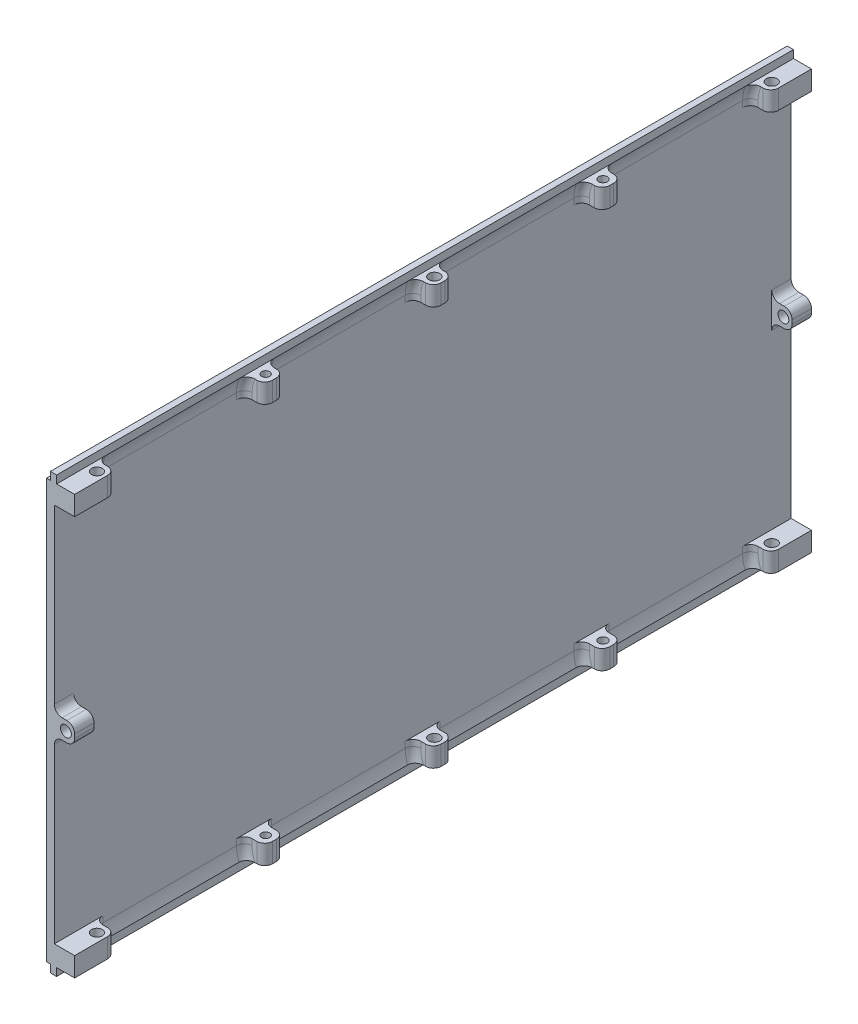
SolidWorks part; units mm, degrees
note: The reader was unsure of these and kept them because the rebuilt part matched: shared geometry of "Sketch4<2>".
ref_plane "Front Plane" through (0, 0, 0) normal (0, 0, 1) x (1, 0, 0)
ref_plane "Top Plane" through (0, 0, 0) normal (0, 1, 0) x (1, 0, 0)
ref_plane "Right Plane" through (0, 0, 0) normal (1, 0, 0) x (0, 0, -1)
sketch "Sketch1" plane through (0, 0, 0) normal (1, 0, 0) x (0, 0, -1)
  line L0 (-95.2867, 0.9102) -> (94.7133, 0.9102) construction
  line L1 (-95.2867, 54.9102) -> (94.7133, 54.9102)
  line L2 (-95.2867, 54.9102) -> (-95.2867, -53.0898)
  line L3 (-95.2867, -53.0898) -> (94.7133, -53.0898)
  line L4 (94.7133, 54.9102) -> (94.7133, -53.0898)
  line L5 (-82.7867, 54.9102) -> (-82.7867, -53.0898) construction
  line L6 (-2.7867, 54.9102) -> (-2.7867, -53.0898) construction
  line L7 (89.2133, 54.9102) -> (89.2133, -53.0898) construction
  dimension "D1" = 190
  dimension "D2" = 108
  dimension "D3" = 12.5
  dimension "D4" = 92.5
  dimension "D5" = 92
extrude "Boss-Extrude1" add sketch "Sketch1" along normal blind 2
sketch "Sketch2" plane through (2, 0, 0) normal (1, 0, 0) x (0, 0, -1)
  line L0 (-0.2867, 54.9102) -> (-0.2867, -53.0898) construction
  line L1 (94.7133, 54.9102) -> (-95.2867, 54.9102) construction
  line L2 (-95.2867, -53.0898) -> (94.7133, -53.0898) construction
  line L3 (-87.2867, 54.9102) -> (-87.2867, -53.0898) construction
  line L4 (86.7133, 54.9102) -> (86.7133, -53.0898) construction
  line L5 (-43.7867, 54.9102) -> (-43.7867, 49.9102) construction
  line L6 (-95.2867, 0.9102) -> (94.7133, 0.9102) construction
  line L7 (-95.2867, 54.9102) -> (-95.2867, -53.0898) construction
  line L8 (94.7133, -53.0898) -> (94.7133, 54.9102) construction
  line L9 (-0.2867, 54.9102) -> (-0.2867, 49.9102) construction
  line L10 (-2.7867, 54.9102) -> (2.2133, 54.9102)
  line L11 (-2.7867, 54.9102) -> (-2.7867, 49.9102)
  line L12 (-2.7867, 49.9102) -> (2.2133, 49.9102)
  line L13 (2.2133, 54.9102) -> (2.2133, 49.9102)
  line L14 (84.2133, 54.9102) -> (89.2133, 54.9102)
  line L15 (84.2133, 54.9102) -> (84.2133, 49.9102)
  line L16 (84.2133, 49.9102) -> (89.2133, 49.9102)
  line L17 (89.2133, 54.9102) -> (89.2133, 49.9102)
  line L18 (-89.7867, 54.9102) -> (-84.7867, 54.9102)
  line L19 (-89.7867, 54.9102) -> (-89.7867, 49.9102)
  line L20 (-89.7867, 49.9102) -> (-84.7867, 49.9102)
  line L21 (-84.7867, 54.9102) -> (-84.7867, 49.9102)
  line L22 (-95.2867, 3.4102) -> (-90.2867, 3.4102)
  line L23 (-95.2867, 3.4102) -> (-95.2867, -1.5898)
  line L24 (-95.2867, -1.5898) -> (-90.2867, -1.5898)
  line L25 (-90.2867, 3.4102) -> (-90.2867, -1.5898)
  line L26 (89.7133, 3.4102) -> (94.7133, 3.4102)
  line L27 (89.7133, 3.4102) -> (89.7133, -1.5898)
  line L28 (89.7133, -1.5898) -> (94.7133, -1.5898)
  line L29 (94.7133, 3.4102) -> (94.7133, -1.5898)
  line L30 (-87.2867, 54.9102) -> (-87.2867, 49.9102) construction
  line L31 (86.7133, 54.9102) -> (86.7133, 49.9102) construction
  line L32 (-95.2867, 0.9102) -> (-90.2867, 0.9102) construction
  line L33 (89.7133, 0.9102) -> (94.7133, 0.9102) construction
  line L34 (86.7133, -53.0898) -> (86.7133, -48.0898) construction
  line L35 (-87.2867, -53.0898) -> (-87.2867, -48.0898) construction
  line L36 (-0.2867, -53.0898) -> (-0.2867, -48.0898) construction
  line L37 (-84.7867, -53.0898) -> (-84.7867, -48.0898)
  line L38 (-89.7867, -48.0898) -> (-84.7867, -48.0898)
  line L39 (-89.7867, -53.0898) -> (-89.7867, -48.0898)
  line L40 (-89.7867, -53.0898) -> (-84.7867, -53.0898)
  line L41 (89.2133, -53.0898) -> (89.2133, -48.0898)
  line L42 (84.2133, -48.0898) -> (89.2133, -48.0898)
  line L43 (84.2133, -53.0898) -> (84.2133, -48.0898)
  line L44 (84.2133, -53.0898) -> (89.2133, -53.0898)
  line L45 (2.2133, -53.0898) -> (2.2133, -48.0898)
  line L46 (-2.7867, -48.0898) -> (2.2133, -48.0898)
  line L47 (-2.7867, -53.0898) -> (-2.7867, -48.0898)
  line L48 (-2.7867, -53.0898) -> (2.2133, -53.0898)
  line L49 (-46.2867, 54.9102) -> (-41.2867, 54.9102)
  line L50 (-89.7867, 54.9102) -> (-95.2867, 54.9102)
  line L51 (-89.7867, 54.9102) -> (-89.7867, 49.9102)
  line L52 (-89.7867, 49.9102) -> (-95.2867, 49.9102)
  line L53 (-95.2867, 54.9102) -> (-95.2867, 49.9102)
  line L54 (-89.7867, -48.0898) -> (-95.2867, -48.0898)
  line L55 (-89.7867, -48.0898) -> (-89.7867, -53.0898)
  line L56 (-89.7867, -53.0898) -> (-95.2867, -53.0898)
  line L57 (-95.2867, -48.0898) -> (-95.2867, -53.0898)
  line L58 (89.2133, 54.9102) -> (94.7133, 54.9102)
  line L59 (89.2133, 54.9102) -> (89.2133, 49.9102)
  line L60 (89.2133, 49.9102) -> (94.7133, 49.9102)
  line L61 (94.7133, 54.9102) -> (94.7133, 49.9102)
  line L62 (89.2133, -48.0898) -> (94.7133, -48.0898)
  line L63 (89.2133, -48.0898) -> (89.2133, -53.0898)
  line L64 (89.2133, -53.0898) -> (94.7133, -53.0898)
  line L65 (94.7133, -48.0898) -> (94.7133, -53.0898)
  line L66 (-46.2867, 54.9102) -> (-46.2867, 49.9102)
  line L67 (-46.2867, 49.9102) -> (-41.2867, 49.9102)
  line L68 (-41.2867, 54.9102) -> (-41.2867, 49.9102)
  line L69 (43.2133, 54.9102) -> (43.2133, 49.9102) construction
  line L70 (40.7133, 54.9102) -> (40.7133, 49.9102)
  line L71 (45.7133, 49.9102) -> (40.7133, 49.9102)
  line L72 (45.7133, 54.9102) -> (45.7133, 49.9102)
  line L73 (45.7133, 54.9102) -> (40.7133, 54.9102)
  line L74 (45.7133, -48.0898) -> (40.7133, -48.0898)
  line L75 (43.2133, -53.0898) -> (43.2133, -48.0898) construction
  line L76 (45.7133, -53.0898) -> (45.7133, -48.0898)
  line L77 (45.7133, -53.0898) -> (40.7133, -53.0898)
  line L78 (40.7133, -53.0898) -> (40.7133, -48.0898)
  line L79 (-43.7867, -53.0898) -> (-43.7867, -48.0898) construction
  line L80 (-41.2867, -53.0898) -> (-41.2867, -48.0898)
  line L81 (-46.2867, -48.0898) -> (-41.2867, -48.0898)
  line L82 (-46.2867, -53.0898) -> (-46.2867, -48.0898)
  line L83 (-46.2867, -53.0898) -> (-41.2867, -53.0898)
  line M26 (-95.2867, 54.9102) -> (-95.2867, -53.0898)
  line M27 (-95.2867, -53.0898) -> (94.7133, -53.0898)
  line M28 (94.7133, -53.0898) -> (94.7133, 54.9102)
  line M29 (94.7133, 54.9102) -> (-95.2867, 54.9102)
  dimension "D1" = 87
  dimension "D2" = 87
  dimension "D3" = 5
  dimension "D4" = 43.5
extrude "Boss-Extrude2" add sketch "Sketch2" along normal blind 5.25 contours L39 L54 M26 M27 | L39 L37 L38 M27 | L25 L22 L24 M26 | L52 L19 M29 M26 | L21 L19 L20 M29 | L13 L11 L12 M29 | L17 L15 L16 M29 | L17 L60 M28 M29 | L27 L28 L26 M28 | L47 L45 L46 M27 | L43 L41 L42 M27 | L62 L41 M27 M28 | L68 L66 L67 M29 | L72 L70 L71 M29 | L82 L80 L81 M27 | L78 L76 L74 M27
sketch "Sketch3" plane through (0, 0, 95.2867) normal (0, 0, 1) x (1, 0, 0)
  line L0 (2, 3.4102) -> (2, -1.5898) construction
  line L1 (8, 0.9102) -> (2, 0.9102) construction
  line L2 (0, 54.9102) -> (0, -53.0898) construction
  circle A0 centre (5, 0.9102) radius 1.4
  dimension "D1" = 2.8
  dimension "D2" = 5
extrude "Cut-Extrude1" cut sketch "Sketch3" against normal through all
sketch "Sketch4" plane through (0, 54.9102, 0) normal (0, 1, 0) x (1, 0, 0)
  line L0 (2.5, 89.2133) -> (2.5, -89.7867) construction
  line L1 (7.25, -0.2867) -> (2.5, -0.2867) construction
  line L2 (0, 94.7133) -> (0, -95.2867) construction
  line L3 (7.25, -43.7867) -> (2.5, -43.7867) construction
  line L6 (7.5, 86.7133) -> (2.5, 86.7133) construction
  line L7 (7.25, -41.2867) -> (7.25, -46.2867) construction
  line L8 (7.5, -87.2867) -> (2.5, -87.2867) construction
  line L9 (7.25, 43.2133) -> (2.5, 43.2133) construction
  line L10 (7.25, 45.7133) -> (7.25, 40.7133) construction
  line L11 (7.25, 2.2133) -> (7.25, -2.7867) construction
  circle A0 centre (5, -0.2867) radius 1.4
  circle A1 centre (5, -87.2867) radius 1.4
  circle A2 centre (5, 86.7133) radius 1.4
  circle A3 centre (5, 43.2133) radius 1.1329
  circle A4 centre (5, -43.7867) radius 1.05
  dimension "D1" = 2.8
  dimension "D2" = 87
  dimension "D3" = 87
  dimension "D4" = 5
extrude "Cut-Extrude2" cut sketch "Sketch4" against normal up to surface (5 mm away) up to face at (4.625, 49.9102, 90.0367)
extrude "Cut-Extrude3" cut sketch "Sketch4<2>" along normal up to surface (5 mm away) from surface at -108 up to face at (5.2812, -48.0898, 88.7242) starting at face at (4.5563, -53.0898, 4.1367)
sketch "Sketch4<2>" plane through (0, 54.9102, 0) normal (0, 1, 0) x (1, 0, 0) same geometry as "Sketch4"
sketch "Sketch5" plane through (0, 54.9102, 0) normal (0, 1, 0) x (1, 0, 0)
  line L0 (7.25, -95.2867) -> (0, -95.2867) construction
  line L1 (1, -95.2867) -> (2.6, -95.2867)
  line L2 (1, -95.2867) -> (1, 94.7133)
  line L3 (1, 94.7133) -> (2.6, 94.7133)
  line L4 (2.6, -95.2867) -> (2.6, 94.7133)
  line L5 (7.25, 94.7133) -> (0, 94.7133) construction
  line L6 (0, 94.7133) -> (0, -95.2867) construction
  dimension "D1" = 1.6
  dimension "D2" = 1
extrude "Boss-Extrude3" add sketch "Sketch5" along normal blind 2
sketch "Sketch6" plane through (0, -53.0898, 0) normal (0, -1, 0) x (1, 0, 0)
  line L0 (7.25, 95.2867) -> (0, 95.2867) construction
  line L1 (1, 95.2867) -> (2.6, 95.2867)
  line L2 (1, 95.2867) -> (1, -94.7133)
  line L3 (1, -94.7133) -> (2.6, -94.7133)
  line L4 (2.6, 95.2867) -> (2.6, -94.7133)
  line L5 (7.25, -94.7133) -> (0, -94.7133) construction
  line L6 (0, 95.2867) -> (0, -94.7133) construction
  dimension "D1" = 1.6
  dimension "D2" = 1
extrude "Boss-Extrude18" add sketch "Sketch6" along normal blind 2
fillet "Fillet1" radius 10 4 edges at (2, 54.9102, -64.9633) (2, 54.9102, 22.0367)
fillet "Fillet2" radius 10 4 edges at (2, 54.9102, -21.4633) (2, 54.9102, 65.5367)
fillet "Fillet3" radius 2 20 edges at (7.25, -1.5898, -92.2133) (7.25, 3.4102, -92.2133) (7.25, 52.4102, 84.7867) (7.25, -1.5898, 92.7867) (7.25, 3.4102, 92.7867) (7.25, -50.5898, 84.7867) (7.25, -50.5898, -84.2133) (7.25, -50.5898, -45.7133) (7.25, -50.5898, -40.7133) (7.25, -50.5898, -2.2133) (7.25, -50.5898, 2.7867) (7.25, -50.5898, 41.2867) (7.25, -50.5898, 46.2867) (7.25, 52.4102, -84.2133) (7.25, 52.4102, -45.7133) (7.25, 52.4102, -40.7133) (7.25, 52.4102, -2.2133) (7.25, 52.4102, 2.7867) (7.25, 52.4102, 41.2867) (7.25, 52.4102, 46.2867)
fillet "Fillet4" radius 2 36 edges at (2, -48.884, -45.7133) (2.1511, -51.4102, -45.7133) (2, -48.884, -2.2133) (2.1511, -51.4102, -2.2133) (2, -48.884, 41.2867) (2.1511, -51.4102, 41.2867) (2.1511, -51.4102, 84.7867) (2, -1.5898, -92.2133) (2.1511, 53.2305, -45.7133) (2, 50.7043, -45.7133) (2.1511, 53.2305, -2.2133) (2, 50.7043, -2.2133) (2.1511, 53.2305, 41.2867) (2, 50.7043, 41.2867) (2.1511, 53.2305, 84.7867) (2, 50.7043, 84.7867) (2, -1.5898, 92.7867) (2, 3.4102, 92.7867) (2, 3.4102, -92.2133) (2, -48.884, -84.2133) (2.1511, -51.4102, -84.2133) (2, -48.884, -40.7133) (2.1511, -51.4102, -40.7133) (2, -48.884, 2.7867) (2.1511, -51.4102, 2.7867) (2, -48.884, 46.2867) (2.1511, -51.4102, 46.2867) (2, 50.7043, -84.2133) (2.1511, 53.2305, -84.2133) (2, 50.7043, -40.7133) (2.1511, 53.2305, -40.7133) (2, 50.7043, 2.7867) (2.1511, 53.2305, 2.7867) (2.1511, 53.2305, 46.2867) (2, 50.7043, 46.2867)
